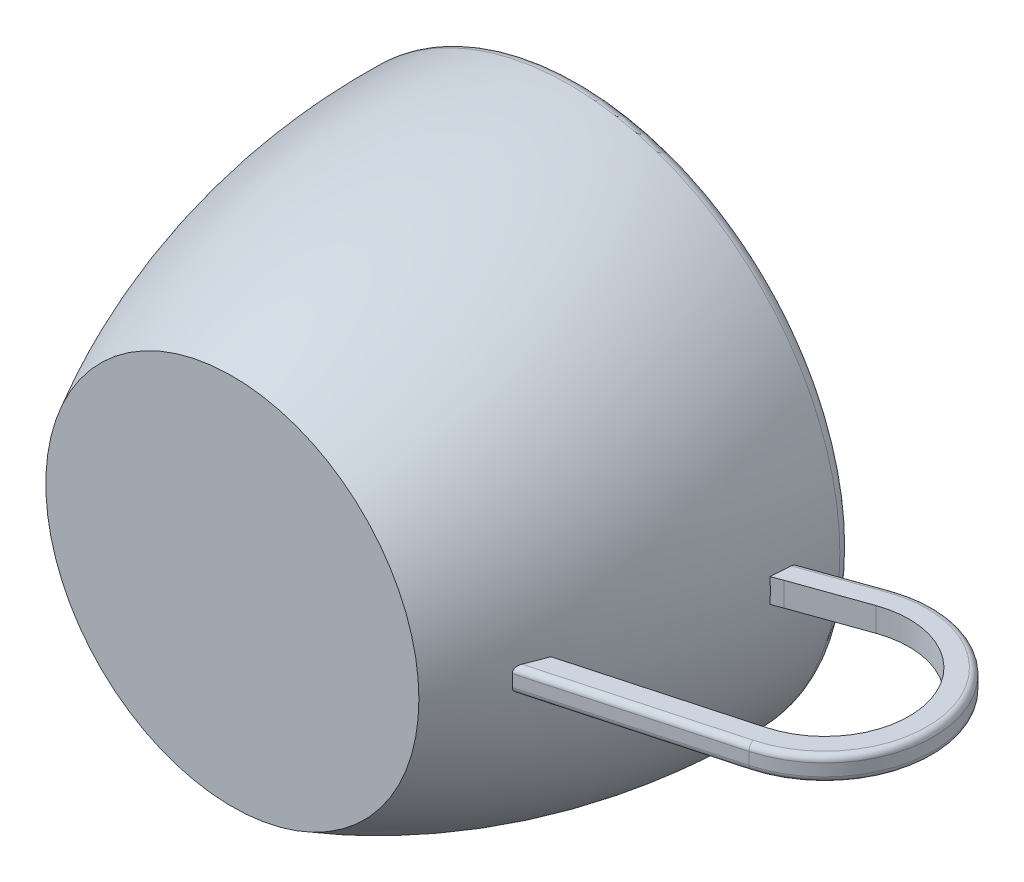
SolidWorks part; units mm, degrees
ref_plane "Front Plane" through (0, 0, 0) normal (0, 0, 1) x (1, 0, 0)
ref_plane "Top Plane" through (0, 0, 0) normal (0, 1, 0) x (1, 0, 0)
ref_plane "Right Plane" through (0, 0, 0) normal (1, 0, 0) x (0, 0, -1)
sketch "Sketch1" plane through (0, 0, 0) normal (0, 1, 0) x (1, 0, 0)
  line L0 (0, -6.322) -> (0, 20.0654) construction
  line L1 (0, 0) -> (-15.5, 0)
  line L2 (0, 2) -> (-14.3055, 2)
  line L3 (0, 0) -> (0, 2)
  arc A0 (-15.5, 0) -> (-22.4771, 28) centre (33.5154, 27.083) cw
  arc A1 (-14.3055, 2) -> (-20.4773, 27.9672) centre (33.5154, 27.083) cw
  arc A2 (-22.4771, 28) -> (-20.4773, 27.9672) centre (-21.4772, 27.9836) cw
  dimension "D2" = 56
  dimension "D1" = 15.5
  dimension "D3" = 28
  dimension "D4" = 2
revolve "Revolve1" add sketch "Sketch1" angle 360 about L0
ref_plane "Plane1" through (0, 0, 0) normal (0, 1, 0) x (1, 0, 0)
sketch "Sketch3" plane through (0, 0, 0) normal (0, 1, 0) x (1, 0, 0)
  line L0 (18.0423, 5.2244) -> (33.4735, 9.453)
  line L1 (22.4298, 24.6073) -> (28.0841, 26.6145)
  line L2 (23.0989, 22.7225) -> (28.7532, 24.7297)
  line L3 (17.5138, 7.1533) -> (32.9449, 11.3819)
  line L4 (22.4298, 24.6073) -> (20.7699, 23.9793)
  line L5 (20.7699, 23.9793) -> (21.4777, 22.1087)
  line L6 (21.4777, 22.1087) -> (23.0989, 22.7225)
  arc A5 (15.5, 0) -> (22.4771, 28) centre (-33.5154, 27.083) ccw construction
  arc A6 (28.0841, 26.6145) -> (33.4735, 9.453) centre (31.0949, 18.133) cw
  arc A7 (28.7532, 24.7297) -> (32.9449, 11.3819) centre (31.0949, 18.133) cw
  arc A9 (17.5138, 7.1533) -> (18.0423, 5.2244) centre (17.7781, 6.1889) ccw
  dimension "D3" = 9
  dimension "D1" = 6
  dimension "D2" = 16
  dimension "D5" = 2
  dimension "D4" = 2
extrude "Boss-Extrude1" add sketch "Sketch3" along normal mid plane 2
fillet "Fillet2" radius 0.5 8 edges at (18.0268, -1, -5.2203) (25.7579, -1, -7.3387) (25.257, -1, -25.6109) (18.0268, 1, -5.2203) (25.7579, 1, -7.3387) (25.257, 1, -25.6109) (39.6814, -1, -20.8295) (39.6814, 1, -20.8295)
